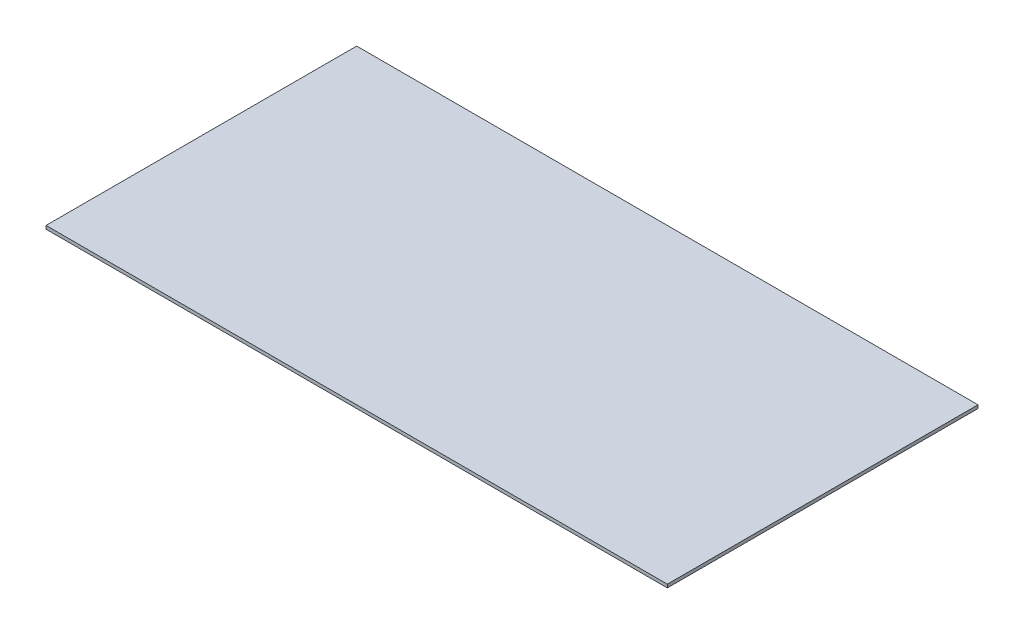
SolidWorks part; units mm, degrees
material "Balsa"
ref_plane "Front Plane" through (0, 0, 0) normal (0, 0, 1) x (1, 0, 0)
ref_plane "Top Plane" through (0, 0, 0) normal (0, 1, 0) x (1, 0, 0)
ref_plane "Right Plane" through (0, 0, 0) normal (1, 0, 0) x (0, 0, -1)
sketch "Sketch1" plane through (0, 0, 0) normal (0, 1, 0) x (1, 0, 0)
  line L1 (-241.3, -120.65) -> (241.3, -120.65)
  line L2 (-241.3, -120.65) -> (-241.3, 120.65)
  line L3 (-241.3, 120.65) -> (241.3, 120.65)
  line L4 (241.3, -120.65) -> (241.3, 120.65)
  line L5 (-241.3, -120.65) -> (241.3, 120.65) construction
  line L6 (-241.3, 120.65) -> (241.3, -120.65) construction
  point P0 (0, 0)
  dimension "D1" = 241.3
  dimension "D2" = 482.6
extrude "Boss-Extrude1" add sketch "Sketch1" along normal blind 2.54
